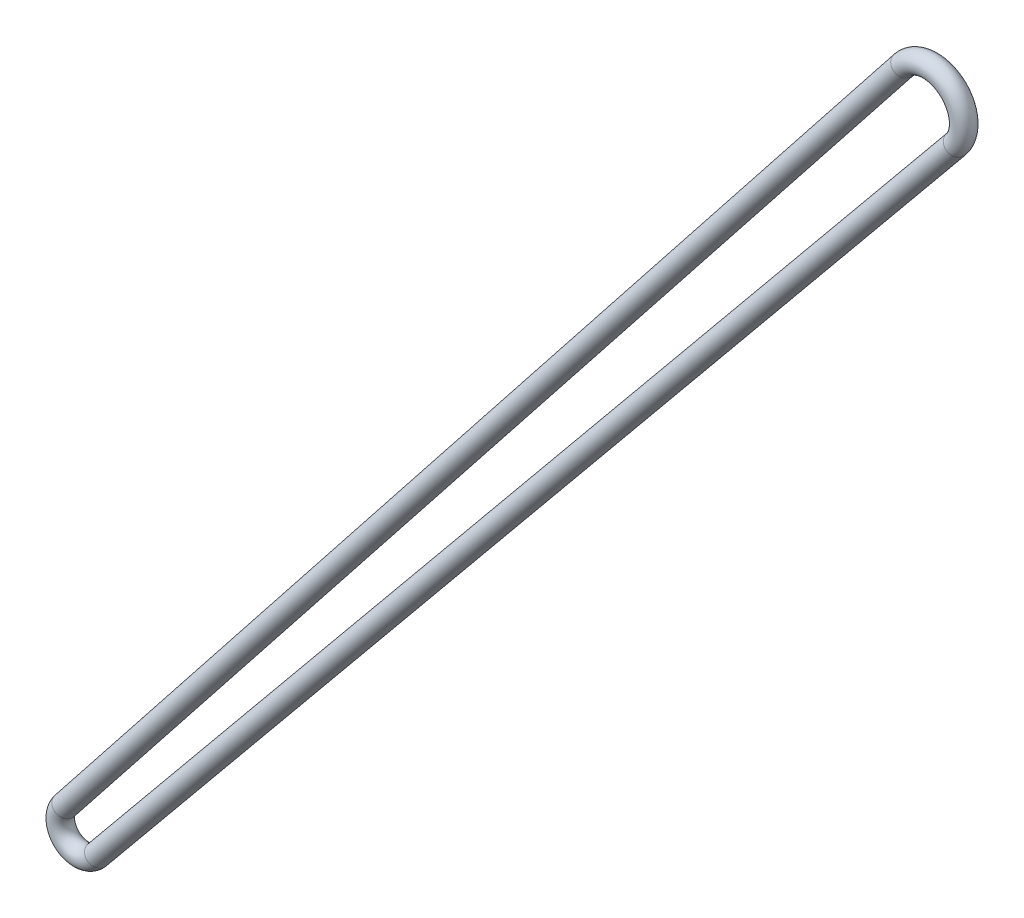
SolidWorks part; units mm, degrees
ref_plane "前视基准面" through (0, 0, 0) normal (0, 0, 1) x (1, 0, 0)
ref_plane "上视基准面" through (0, 0, 0) normal (0, 1, 0) x (1, 0, 0)
ref_plane "右视基准面" through (0, 0, 0) normal (1, 0, 0) x (0, 0, -1)
sketch "草图2" plane through (0, 0, 0) normal (0, 0, 1) x (1, 0, 0)
  line L0 (0, 0) -> (1, 0) construction
  line L1 (0, 0) -> (0, 1) construction
  line L2 (-2.4317, 1.9227) -> (121.9377, 159.219)
  line L3 (129.7225, 152.943) -> (2.3949, -1.9684)
  arc A0 (2.3949, -1.9684) -> (-2.4317, 1.9227) centre (0, 0) cw
  arc A1 (121.9377, 159.219) -> (129.7225, 152.943) centre (125.8599, 156.1179) cw
sweep "扫描19" add path "草图2" circular profile diameter 3 parameters "D3"=3
